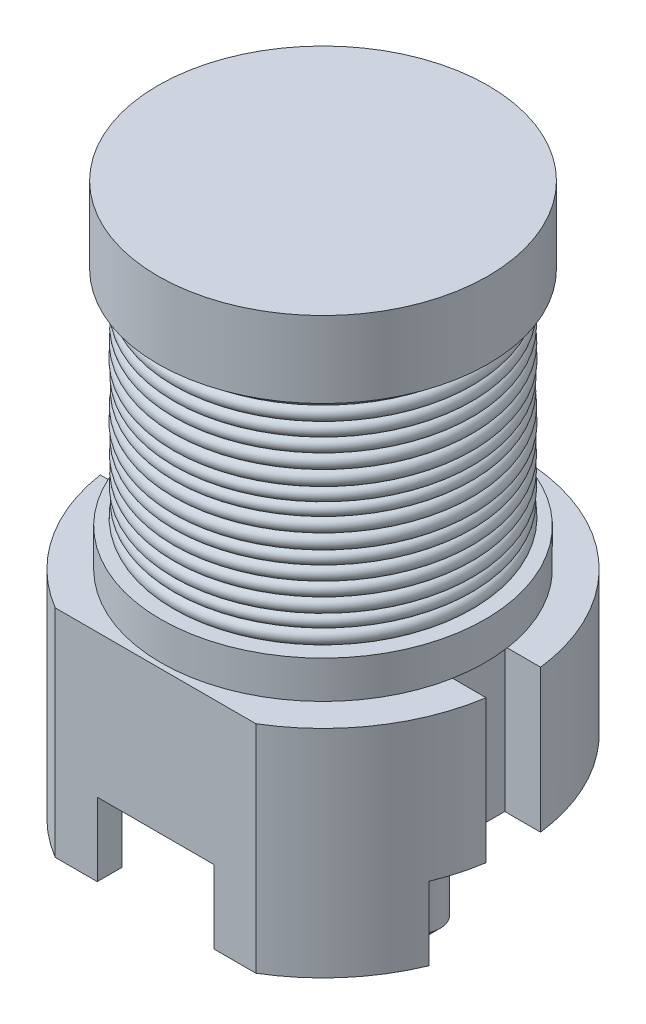
SolidWorks part; units mm, degrees
note: '?' marks a value the reader was unsure of.
ref_plane "Plan de face" through (0, 0, 0) normal (0, 0, 1) x (1, 0, 0)
ref_plane "Plan de dessus" through (0, 0, 0) normal (0, 1, 0) x (1, 0, 0)
ref_plane "Plan de droite" through (0, 0, 0) normal (1, 0, 0) x (0, 0, -1)
ref_axis "Axe2" through (0, -41.3183, 0) along (0, 1, 0)?
sketch "Esquisse1" plane through (0, 0, 0) normal (0, 0, 1) x (1, 0, 0)
  line L0 (0, 27.3635) -> (0, 0) construction
  line L1 (0, 27.2882) -> (6.7685, 27.2882)
  line L2 (0, 4.6406) -> (8.006, 4.6406)
  line L3 (0, 27.2882) -> (0, 4.6406)
  line L4 (5.9078, 15.0393) -> (5.9078, 15.0507)
  line L5 (8.006, 4.6406) -> (8.006, 7.6461)
  line L6 (8.006, 13.5011) -> (7.0864, 13.5011)
  line L7 (8.006, 13.5011) -> (8.006, 7.6461)
  line L10 (6.6498, 15.0393) -> (5.9078, 15.0393)
  line L11 (6.6498, 15.0393) -> (6.6498, 13.5011)
  line L14 (6.7685, 27.2882) -> (6.7685, 24.1638)
  line L15 (6.7685, 24.1638) -> (5.9078, 24.1638)
  line L16 (5.9078, 24.1638) -> (5.9078, 15.0393) construction
  line L17 (7.0864, 13.5011) -> (6.6498, 13.5011)
  arc A0 (5.9078, 24.1638) -> (5.9078, 23.5638) centre (5.9078, 23.8638) cw
  arc A1 (5.9078, 23.5638) -> (5.9078, 22.9838) centre (5.9078, 23.2738) cw
  arc A2 (5.9078, 22.9838) -> (5.9078, 22.4255) centre (5.9078, 22.7047) cw
  arc A3 (5.9078, 22.4255) -> (5.9078, 21.8636) centre (5.9078, 22.1445) cw
  arc A4 (5.9078, 21.8636) -> (5.9078, 21.2785) centre (5.9078, 21.571) cw
  arc A5 (5.9078, 21.2785) -> (5.9078, 20.6735) centre (5.9078, 20.976) cw
  arc A6 (5.9078, 20.6735) -> (5.9078, 20.1265) centre (5.9078, 20.4) cw
  arc A7 (5.9078, 20.1265) -> (5.9078, 19.6016) centre (5.9078, 19.864) cw
  arc A8 (5.9078, 19.6016) -> (5.9078, 19.0241) centre (5.9078, 19.3128) cw
  arc A9 (5.9078, 19.0241) -> (5.9078, 18.4229) centre (5.9078, 18.7235) cw
  arc A10 (5.9078, 18.4229) -> (5.9078, 17.8807) centre (5.9078, 18.1518) cw
  arc A11 (5.9078, 17.8807) -> (5.9078, 17.3105) centre (5.9078, 17.5956) cw
  arc A12 (5.9078, 17.3105) -> (5.9078, 16.7493) centre (5.9078, 17.0299) cw
  arc A13 (5.9078, 16.7493) -> (5.9078, 16.1699) centre (5.9078, 16.4596) cw
  arc A14 (5.9078, 16.1699) -> (5.9078, 15.6435) centre (5.9078, 15.9067) cw
  arc A15 (5.9078, 15.6435) -> (5.9078, 15.0507) centre (5.9078, 15.3471) cw
revolve "Révolution1" add sketch "Esquisse1" angle 360 about L3
sketch "Esquisse2" plane through (0, 4.6406, 0) normal (0, -1, 0) x (1, 0, 0)
  line L0 (4.1135, 6.8684) -> (2.388, 6.8684)
  line L1 (2.388, 6.8684) -> (2.388, 5.8606)
  line L2 (7.3975, 3.0616) -> (5.2096, 3.0616)
  line L3 (2.388, -5.2456) -> (2.388, -7.6415)
  line L4 (0, 9.9321) -> (0, -12.0997) construction
  line L5 (-4.1135, 6.8684) -> (-2.388, 6.8684)
  line L6 (-2.388, 6.8684) -> (-2.388, 5.8606)
  line L7 (-7.3975, 3.0616) -> (-5.2096, 3.0616)
  line L8 (-2.388, -5.2456) -> (-2.388, -7.6415)
  circle A0 centre (0, 0) radius 8.006
  arc A1 (2.388, -5.2456) -> (-0.021, -5.8221) centre (0.025, -0.6932) cw
  arc A2 (2.388, 5.8606) -> (5.2096, 3.0616) centre (0, 0.6317) cw
  arc A3 (-2.388, 5.8606) -> (-5.2096, 3.0616) centre (0, 0.6317) ccw
  arc A4 (-2.388, -5.2456) -> (0.021, -5.8221) centre (-0.025, -0.6932) ccw
extrude "Enlèv. mat.-Extru.1" cut sketch "Esquisse2" against normal blind 3
sketch "Esquisse3" plane through (0, 7.6406, 0) normal (0, -1, 0) x (1, 0, 0)
  circle A0 centre (-3.7156, 0) radius 1.0274
  circle A1 centre (3.8448, 0) radius 0.9564
extrude "Boss.-Extru.1" add sketch "Esquisse3" along normal blind 5
sketch "Esquisse4" plane through (0, 7.6406, 0) normal (0, -1, 0) x (1, 0, 0)
  line L0 (-4.1135, 6.8684) -> (4.1135, 6.8684)
  arc A0 (-4.1135, 6.8684) -> (4.1135, 6.8684) centre (0, 0) cw
extrude "Enlèv. mat.-Extru.2" cut sketch "Esquisse4" against normal through all
chamfer "Chanfrein1" distance 0.5 angle 45 2 edges at (-3.7156, 2.6406, -1.0274) (3.8448, 2.6406, -0.9564)
sketch "Esquisse5" plane through (0, 7.6406, 0) normal (0, -1, 0) x (1, 0, 0)
  line L0 (7.9118, 1.2246) -> (6.4772, 1.2246)
  line L1 (6.4772, 1.2246) -> (6.4772, -0.9765)
  line L2 (6.4772, -0.9765) -> (7.9462, -0.9765)
  line L3 (0, 9.9321) -> (0, -8.3989) construction
  line L4 (0, 9.9321) -> (0, -12.0997) construction
  line L5 (-6.4772, -0.9765) -> (-7.9462, -0.9765)
  line L6 (-6.4772, 1.2246) -> (-6.4772, -0.9765)
  line L7 (-7.9118, 1.2246) -> (-6.4772, 1.2246)
  circle A0 centre (0, 0) radius 8.006 construction
  arc A1 (7.9118, 1.2246) -> (7.9462, -0.9765) centre (0, 0) cw
  arc A2 (-7.9118, 1.2246) -> (-7.9462, -0.9765) centre (0, 0) ccw
extrude "Enlèv. mat.-Extru.3" cut sketch "Esquisse5" against normal blind 5.865
